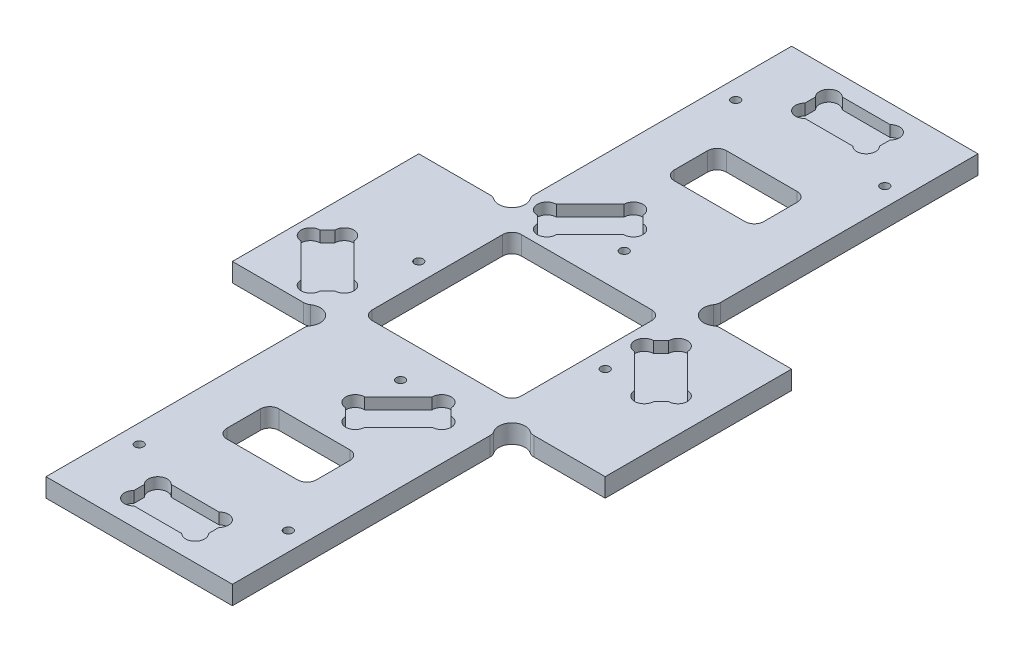
SolidWorks part; units mm, degrees
ref_plane "Front" through (0, 0, 0) normal (0, 0, 1) x (1, 0, 0)
ref_plane "Top" through (0, 0, 0) normal (0, 1, 0) x (1, 0, 0)
ref_plane "Right" through (0, 0, 0) normal (1, 0, 0) x (0, 0, -1)
sketch "Sketch1" plane through (0, 0, 0) normal (0, 1, 0) x (1, 0, 0)
  line L0 (45.4057, 247.3952) -> (45.4057, -6.6048) construction
  line L1 (13.6557, -6.6048) -> (77.1557, -6.6048)
  line L2 (13.6557, -6.6048) -> (13.6557, 247.3952)
  line L3 (13.6557, 247.3952) -> (77.1557, 247.3952)
  line L4 (77.1557, -6.6048) -> (77.1557, 247.3952)
  line L5 (13.6557, 152.1452) -> (-18.0943, 152.1452)
  line L6 (13.6557, 152.1452) -> (13.6557, 88.6452)
  line L7 (13.6557, 88.6452) -> (-18.0943, 88.6452)
  line L8 (-18.0943, 152.1452) -> (-18.0943, 88.6452)
  line L9 (77.1557, 88.6452) -> (108.9057, 88.6452)
  line L10 (108.9057, 152.1452) -> (108.9057, 88.6452)
  line L11 (77.1557, 152.1452) -> (108.9057, 152.1452)
  line L12 (77.1557, 152.1452) -> (77.1557, 88.6452)
  dimension "D1" = 63.5
  dimension "D2" = 254
  dimension "D3" = 31.75
  dimension "D4" = 63.5
  dimension "D5" = 95.25
extrude "Boss-Extrude1" add sketch "Sketch1" along normal blind 6.35 contours L5 L8 L7 L2 | L0 L3 L2 L1 | L3 L0 L1 L4 | L11 L4 L9 L10 region at (61.2807, 0, -120.3952) region at (29.5307, 0, -120.3952) region at (-2.2193, 0, -120.3952) region at (93.0307, 0, -120.3952)
sketch "Sketch2" plane through (0, 6.35, 0) normal (0, 1, 0) x (1, 0, 0)
  line L0 (13.6557, 88.6452) -> (77.1557, 152.1452) construction
  line L1 (77.1557, 152.1452) -> (77.1557, 88.6452) construction
  line L2 (77.1557, 88.6452) -> (45.4057, 120.3952) construction
  line L3 (45.4057, 120.3952) -> (45.4057, 152.1452) construction
  line L4 (45.4057, 152.1452) -> (13.6557, 152.1452) construction
  line L5 (13.6557, 152.1452) -> (45.4057, 120.3952) construction
  line L6 (2.3005, 109.6188) -> (-6.6798, 100.6386) construction
  line L7 (11.2807, 100.6386) -> (-6.6798, 118.5991)
  line L8 (-6.6798, 118.5991) -> (11.2807, 100.6386)
  line L9 (-6.6798, 118.5991) -> (-15.6601, 109.6188)
  line L10 (11.2807, 100.6386) -> (2.3005, 91.6583)
  line L11 (-15.6601, 109.6188) -> (2.3005, 91.6583)
  line L23 (11.2807, 100.6386) -> (2.3005, 91.6583)
  line L28 (43.9231, 166.4458) -> (25.9626, 148.4853)
  line L29 (43.9231, 166.4458) -> (34.9428, 175.4261)
  line L30 (34.9428, 175.4261) -> (16.9823, 157.4655)
  line L31 (25.9626, 148.4853) -> (16.9823, 157.4655)
  line L36 (43.9231, 166.4458) -> (34.9428, 175.4261)
  line L38 (6.7906, 96.1485) -> (-11.1699, 114.109) construction
  line L43 (91.7698, 115.8429) -> (73.8093, 133.8034)
  line L44 (91.7698, 115.8429) -> (100.7501, 124.8232)
  line L45 (100.7501, 124.8232) -> (82.7895, 142.7837)
  line L46 (73.8093, 133.8034) -> (82.7895, 142.7837)
  line L51 (91.7698, 115.8429) -> (100.7501, 124.8232)
  line L58 (41.1669, 67.9962) -> (59.1274, 85.9567)
  line L59 (41.1669, 67.9962) -> (50.1472, 59.0159)
  line L60 (50.1472, 59.0159) -> (68.1077, 76.9765)
  line L61 (59.1274, 85.9567) -> (68.1077, 76.9765)
  line L66 (41.1669, 67.9962) -> (50.1472, 59.0159)
  point P15 (2.3005, 109.6188)
  point P64 (42.545, 117.221)
  dimension "D1" = 22.86
  dimension "D2" = 25.4
  dimension "D3" = 12.7
  dimension "D7" = 38.1
  dimension "D6" = 4
extrude "Cut-Extrude14" cut sketch "Sketch2" against normal blind 3.81 contours L9 L11 L10 L7 | L31 L28 L29 L30 | L46 L43 L44 L45 | L61 L58 L59 L60 region at (-2.1897, 6.35, -105.1287) region at (30.4527, 6.35, -161.9557) region at (87.2797, 6.35, -129.3133) region at (54.6373, 6.35, -72.4863)
sketch "Sketch14" plane through (0, 6.35, 0) normal (0, 1, 0) x (1, 0, 0)
  line L0 (45.4057, -6.6048) -> (45.4057, 247.3952) construction
  line L1 (13.6557, -6.6048) -> (77.1557, -6.6048) construction
  line L2 (13.6557, 247.3952) -> (77.1557, 247.3952) construction
  line L3 (-18.0943, 120.3952) -> (108.9057, 120.3952) construction
  line L4 (32.7057, 241.0452) -> (58.1057, 241.0452)
  line L5 (32.7057, 241.0452) -> (32.7057, 228.3452)
  line L6 (32.7057, 228.3452) -> (58.1057, 228.3452)
  line L7 (58.1057, 241.0452) -> (58.1057, 228.3452)
  line L8 (32.7057, 241.0452) -> (58.1057, 228.3452) construction
  line L9 (32.7057, 228.3452) -> (58.1057, 241.0452) construction
  line L10 (-18.0943, 152.1452) -> (-18.0943, 88.6452) construction
  line L11 (108.9057, 152.1452) -> (108.9057, 88.6452) construction
  line L12 (32.7057, 12.4452) -> (58.1057, 12.4452)
  line L13 (58.1057, -0.2548) -> (58.1057, 12.4452)
  line L14 (32.7057, -0.2548) -> (58.1057, -0.2548)
  line L15 (32.7057, -0.2548) -> (32.7057, 12.4452)
  point P6 (45.4057, 234.6952)
  dimension "D1" = 12.7
  dimension "D2" = 25.4
  dimension "D3" = 6.35
extrude "Cut-Extrude16" cut sketch "Sketch14" against normal blind 3.81
sketch "Sketch15" plane through (0, 6.35, 0) normal (0, 1, 0) x (1, 0, 0)
  line L0 (45.4057, 247.3952) -> (45.4057, -6.6048) construction
  line L1 (13.6557, 247.3952) -> (77.1557, 247.3952) construction
  line L2 (13.6557, -6.6048) -> (77.1557, -6.6048) construction
  line L3 (45.4057, -6.6048) -> (108.9057, 120.3952) construction
  line L4 (108.9057, 152.1452) -> (108.9057, 88.6452) construction
  line L5 (108.9057, 120.3952) -> (-18.0943, 120.3952) construction
  line L6 (-18.0943, 152.1452) -> (-18.0943, 88.6452) construction
  line L7 (30.1657, 35.3052) -> (60.6457, 35.3052)
  line L8 (20.0057, 94.9952) -> (70.8057, 94.9952)
  line L9 (20.0057, 94.9952) -> (20.0057, 145.7952)
  line L10 (20.0057, 145.7952) -> (70.8057, 145.7952)
  line L11 (70.8057, 94.9952) -> (70.8057, 145.7952)
  line L12 (20.0057, 94.9952) -> (70.8057, 145.7952) construction
  line L13 (20.0057, 145.7952) -> (70.8057, 94.9952) construction
  line L14 (30.1657, 187.7052) -> (60.6457, 187.7052)
  line L15 (30.1657, 187.7052) -> (30.1657, 205.4852)
  line L16 (30.1657, 205.4852) -> (60.6457, 205.4852)
  line L17 (60.6457, 187.7052) -> (60.6457, 205.4852)
  line L18 (30.1657, 187.7052) -> (60.6457, 205.4852) construction
  line L19 (30.1657, 205.4852) -> (60.6457, 187.7052) construction
  line L20 (60.6457, 53.0852) -> (60.6457, 35.3052)
  line L21 (30.1657, 53.0852) -> (60.6457, 53.0852)
  line L22 (30.1657, 53.0852) -> (30.1657, 35.3052)
  point P6 (45.4057, 120.3952)
  point P17 (45.4057, 196.5952)
  dimension "D1" = 50.8
  dimension "D2" = 50.8
  dimension "D3" = 17.78
  dimension "D4" = 30.48
  dimension "D5" = 50.8
extrude "Cut-Extrude17" cut sketch "Sketch15" against normal through all
fillet "Fillet1" radius 3.175 12 edges at (30.1657, 3.175, -205.4852) (30.1657, 3.175, -187.7052) (60.6457, 3.175, -187.7052) (60.6457, 3.175, -205.4852) (60.6457, 3.175, -53.0852) (30.1657, 3.175, -53.0852) (30.1657, 3.175, -35.3052) (60.6457, 3.175, -35.3052) (70.8057, 3.175, -94.9952) (70.8057, 3.175, -145.7952) (20.0057, 3.175, -145.7952) (20.0057, 3.175, -94.9952)
sketch "Sketch16" plane through (0, 6.35, 0) normal (0, 1, 0) x (1, 0, 0)
  line L0 (45.4057, -6.6048) -> (45.4057, 247.3952) construction
  line L1 (13.6557, 88.6452) -> (10.4807, 88.6452)
  line L2 (13.6557, 88.6452) -> (13.6557, 85.4702)
  line L3 (13.6557, 85.4702) -> (10.4807, 85.4702)
  line L4 (10.4807, 88.6452) -> (10.4807, 85.4702)
  line L5 (13.6557, -6.6048) -> (77.1557, -6.6048) construction
  line L6 (13.6557, 247.3952) -> (77.1557, 247.3952) construction
  line L7 (45.4057, 247.3952) -> (108.9057, 120.3952) construction
  line L8 (108.9057, 152.1452) -> (108.9057, 88.6452) construction
  line L9 (108.9057, 120.3952) -> (-18.0943, 120.3952) construction
  line L10 (-18.0943, 152.1452) -> (-18.0943, 88.6452) construction
  line L11 (77.1557, 85.4702) -> (80.3307, 85.4702)
  line L12 (80.3307, 88.6452) -> (80.3307, 85.4702)
  line L13 (77.1557, 88.6452) -> (80.3307, 88.6452)
  line L14 (77.1557, 88.6452) -> (77.1557, 85.4702)
  line L16 (77.1557, 152.1452) -> (77.1557, 155.3202)
  line L17 (77.1557, 152.1452) -> (80.3307, 152.1452)
  line L18 (80.3307, 152.1452) -> (80.3307, 155.3202)
  line L19 (77.1557, 155.3202) -> (80.3307, 155.3202)
  line L20 (13.6557, 155.3202) -> (10.4807, 155.3202)
  line L21 (10.4807, 152.1452) -> (10.4807, 155.3202)
  line L22 (13.6557, 152.1452) -> (10.4807, 152.1452)
  line L23 (13.6557, 152.1452) -> (13.6557, 155.3202)
  circle A0 centre (10.4807, 85.4702) radius 4.4901
  circle A1 centre (80.3307, 85.4702) radius 4.4901
  circle A2 centre (80.3307, 155.3202) radius 4.4901
  circle A3 centre (10.4807, 155.3202) radius 4.4901
  dimension "D1" = 3.175
  dimension "D2" = 3.175
extrude "Cut-Extrude18" cut sketch "Sketch16" against normal through all contours L1 A0 L2 L3 L4 | L1 L4 L3 L2 | L13 L14 L11 L12 | L14 A1 L13 L12 L11 | L19 L16 L17 L18 | L17 A2 L16 L19 L18 | L22 L23 L20 L21 | L23 A3 L22 L21 L20 region at (12.0682, 6.35, -87.0577) region at (10.1802, 6.35, -85.1697) region at (78.7432, 6.35, -87.0577) region at (80.6312, 6.35, -85.1697) region at (78.7432, 6.35, -153.7327) region at (80.6312, 6.35, -155.6206) region at (12.0682, 6.35, -153.7327) region at (10.1802, 6.35, -155.6206)
fillet "Fillet2" radius 3.175 8 edges at (13.6557, 3.175, -158.4952) (7.3057, 3.175, -152.1452) (77.1557, 3.175, -158.4952) (83.5057, 3.175, -152.1452) (77.1557, 3.175, -82.2952) (83.5057, 3.175, -88.6452) (13.6557, 3.175, -82.2952) (7.3057, 3.175, -88.6452)
sketch "Sketch17" plane through (0, 6.35, 0) normal (0, 1, 0) x (1, 0, 0)
  line L0 (45.4057, -6.6048) -> (45.4057, 247.3952) construction
  line L1 (13.6557, -6.6048) -> (77.1557, -6.6048) construction
  line L2 (13.6557, 247.3952) -> (77.1557, 247.3952) construction
  line L3 (45.4057, 247.3952) -> (108.9057, 120.3952) construction
  line L4 (108.9057, 152.1452) -> (108.9057, 88.6452) construction
  line L5 (108.9057, 120.3952) -> (-18.0943, 120.3952) construction
  line L6 (-18.0943, 152.1452) -> (-18.0943, 88.6452) construction
  line L7 (-18.0943, 120.3952) -> (32.7057, 6.0952) construction
  line L8 (32.7057, 12.4452) -> (32.7057, -0.2548) construction
  line L9 (32.7057, 6.0952) -> (58.1057, 6.0952) construction
  line L10 (58.1057, -0.2548) -> (58.1057, 12.4452) construction
  line L11 (32.7057, 12.4452) -> (34.9917, 12.4452)
  line L12 (32.7057, 12.4452) -> (32.7057, 10.1592)
  line L13 (34.9917, 12.4452) -> (34.9917, 10.1592)
  line L14 (32.7057, 10.1592) -> (34.9917, 10.1592)
  line L15 (58.1057, 12.4452) -> (32.7057, 12.4452) construction
  line L16 (34.9917, -0.2548) -> (34.9917, 2.0312)
  line L17 (32.7057, 2.0312) -> (34.9917, 2.0312)
  line L18 (32.7057, -0.2548) -> (32.7057, 2.0312)
  line L19 (32.7057, -0.2548) -> (34.9917, -0.2548)
  line L20 (58.1057, -0.2548) -> (55.8197, -0.2548)
  line L21 (58.1057, -0.2548) -> (58.1057, 2.0312)
  line L22 (58.1057, 2.0312) -> (55.8197, 2.0312)
  line L23 (55.8197, -0.2548) -> (55.8197, 2.0312)
  line L24 (55.8197, 12.4452) -> (55.8197, 10.1592)
  line L25 (58.1057, 10.1592) -> (55.8197, 10.1592)
  line L26 (58.1057, 12.4452) -> (58.1057, 10.1592)
  line L27 (58.1057, 12.4452) -> (55.8197, 12.4452)
  line L28 (58.1057, 241.0452) -> (58.1057, 238.7592)
  line L29 (58.1057, 238.7592) -> (55.8197, 238.7592)
  line L30 (55.8197, 241.0452) -> (55.8197, 238.7592)
  line L31 (58.1057, 241.0452) -> (55.8197, 241.0452)
  line L32 (58.1057, 228.3452) -> (55.8197, 228.3452)
  line L33 (58.1057, 228.3452) -> (58.1057, 230.6312)
  line L34 (58.1057, 230.6312) -> (55.8197, 230.6312)
  line L35 (55.8197, 228.3452) -> (55.8197, 230.6312)
  line L36 (34.9917, 228.3452) -> (34.9917, 230.6312)
  line L37 (32.7057, 230.6312) -> (34.9917, 230.6312)
  line L38 (32.7057, 228.3452) -> (32.7057, 230.6312)
  line L39 (32.7057, 228.3452) -> (34.9917, 228.3452)
  line L40 (32.7057, 241.0452) -> (34.9917, 241.0452)
  line L41 (32.7057, 241.0452) -> (32.7057, 238.7592)
  line L42 (32.7057, 238.7592) -> (34.9917, 238.7592)
  line L43 (34.9917, 241.0452) -> (34.9917, 238.7592)
  circle A0 centre (34.9917, 10.1592) radius 3.2329
  circle A1 centre (34.9917, 2.0312) radius 3.2329
  circle A2 centre (55.8197, 2.0312) radius 3.2329
  circle A3 centre (55.8197, 10.1592) radius 3.2329
  circle A4 centre (55.8197, 238.7592) radius 3.2329
  circle A5 centre (55.8197, 230.6312) radius 3.2329
  circle A6 centre (34.9917, 230.6312) radius 3.2329
  circle A7 centre (34.9917, 238.7592) radius 3.2329
  dimension "D1" = 2.286
  dimension "D2" = 2.286
extrude "Cut-Extrude19" cut sketch "Sketch17" against normal blind 3.81 contours L43 L40 L41 L42 | L41 A7 L40 L43 L42 | L31 A4 L28 L29 L30 | L28 L31 L30 L29 | L33 A5 L32 L35 L34 | L35 L32 L33 L34 | L39 A6 L38 L37 L36 | L38 L39 L36 L37 | L19 A1 L18 L17 L16 | L18 L19 L16 L17 | L12 A0 L11 L13 L14 | L12 L14 L13 L11 | L27 A3 L26 L25 L24 | L26 L27 L24 L25 | L21 A2 L20 L23 L22 | L23 L20 L21 L22 region at (33.8487, 6.35, -11.3022) region at (35.208, 6.35, -9.9428) region at (33.8487, 6.35, -0.8882) region at (35.208, 6.35, -2.2475) region at (56.9627, 6.35, -0.8882) region at (55.6033, 6.35, -2.2475) region at (56.9627, 6.35, -11.3022) region at (55.6033, 6.35, -9.9428) region at (56.9627, 6.35, -239.9022) region at (55.6033, 6.35, -238.5428) region at (56.9627, 6.35, -229.4882) region at (55.6033, 6.35, -230.8475) region at (33.8487, 6.35, -229.4882) region at (35.208, 6.35, -230.8475) region at (33.8487, 6.35, -239.9022) region at (35.208, 6.35, -238.5428)
sketch "Sketch18" plane through (0, 6.35, 0) normal (0, 1, 0) x (1, 0, 0)
  line L0 (-15.6601, 109.6188) -> (-14.0436, 111.2353)
  line L1 (-15.6601, 109.6188) -> (-14.0436, 108.0024)
  line L2 (-14.0436, 111.2353) -> (-12.4272, 109.6188)
  line L3 (-14.0436, 108.0024) -> (-12.4272, 109.6188)
  line L4 (-6.6798, 118.5991) -> (-15.6601, 109.6188) construction
  line L5 (-11.1699, 114.109) -> (6.7906, 96.1485) construction
  line L6 (11.2807, 100.6386) -> (2.3005, 91.6583) construction
  line L7 (6.7906, 96.1485) -> (2.3005, 109.6188) construction
  line L8 (11.2807, 100.6386) -> (-6.6798, 118.5991) construction
  line L9 (2.3005, 109.6188) -> (-6.6798, 100.6386) construction
  line L10 (-15.6601, 109.6188) -> (2.3005, 91.6583) construction
  line L11 (-8.2962, 116.9827) -> (-6.6798, 115.3662)
  line L12 (-5.0634, 116.9827) -> (-6.6798, 115.3662)
  line L13 (-6.6798, 118.5991) -> (-5.0634, 116.9827)
  line L14 (-6.6798, 118.5991) -> (-8.2962, 116.9827)
  line L15 (11.2807, 100.6386) -> (9.6643, 99.0221)
  line L16 (11.2807, 100.6386) -> (9.6643, 102.255)
  line L17 (9.6643, 102.255) -> (8.0478, 100.6386)
  line L18 (9.6643, 99.0221) -> (8.0478, 100.6386)
  line L19 (3.9169, 93.2748) -> (2.3005, 94.8912)
  line L20 (0.684, 93.2748) -> (2.3005, 94.8912)
  line L21 (2.3005, 91.6583) -> (0.684, 93.2748)
  line L22 (2.3005, 91.6583) -> (3.9169, 93.2748)
  line L23 (45.4057, 145.7952) -> (45.4057, 94.9952) construction
  line L24 (67.6307, 145.7952) -> (23.1807, 145.7952) construction
  line L25 (23.1807, 94.9952) -> (67.6307, 94.9952) construction
  line L26 (45.4057, 94.9952) -> (70.8057, 120.3952) construction
  line L27 (70.8057, 98.1702) -> (70.8057, 142.6202) construction
  line L28 (70.8057, 120.3952) -> (20.0057, 120.3952) construction
  line L29 (20.0057, 142.6202) -> (20.0057, 98.1702) construction
  circle A0 centre (-12.4272, 109.6188) radius 3.2329
  circle A1 centre (-6.6798, 115.3662) radius 3.2329
  circle A2 centre (8.0478, 100.6386) radius 3.2329
  circle A3 centre (2.3005, 94.8912) radius 3.2329
  dimension "D1" = 2.286
  dimension "D2" = 2.286
extrude "Cut-Extrude20" cut sketch "Sketch18" against normal blind 3.81 contours L1 L3 L2 L0 | L1 A0 L0 L2 L3 | L13 L14 L11 L12 | L14 A1 L13 L12 L11 | L18 L15 L16 L17 | L16 A2 L15 L18 L17 | L21 L22 L19 L20 | L22 A3 L21 L20 L19 region at (-14.0436, 6.35, -109.6188) region at (-12.1212, 6.35, -109.6188) region at (-6.6798, 6.35, -116.9827) region at (-6.6798, 6.35, -115.0602) region at (9.6643, 6.35, -100.6386) region at (7.7419, 6.35, -100.6386) region at (2.3005, 6.35, -93.2748) region at (2.3005, 6.35, -95.1972)
sketch "Sketch19" plane through (0, 6.35, 0) normal (0, 1, 0) x (1, 0, 0)
  line L0 (34.9428, 175.4261) -> (33.3264, 173.8096)
  line L1 (34.9428, 175.4261) -> (36.5593, 173.8096)
  line L2 (33.3264, 173.8096) -> (34.9428, 172.1932)
  line L3 (36.5593, 173.8096) -> (34.9428, 172.1932)
  line L4 (43.9231, 166.4458) -> (34.9428, 175.4261) construction
  line L5 (34.9428, 175.4261) -> (16.9823, 157.4655) construction
  line L6 (39.433, 170.9359) -> (21.4725, 152.9754) construction
  line L7 (25.9626, 148.4853) -> (16.9823, 157.4655) construction
  line L8 (25.9626, 166.4458) -> (34.9428, 157.4655) construction
  line L9 (43.9231, 166.4458) -> (25.9626, 148.4853) construction
  line L11 (42.3067, 164.8294) -> (40.6902, 166.4458)
  line L12 (42.3067, 168.0622) -> (40.6902, 166.4458)
  line L13 (43.9231, 166.4458) -> (42.3067, 168.0622)
  line L14 (43.9231, 166.4458) -> (42.3067, 164.8294)
  line L15 (25.9626, 148.4853) -> (27.579, 150.1017)
  line L16 (25.9626, 148.4853) -> (24.3461, 150.1017)
  line L17 (24.3461, 150.1017) -> (25.9626, 151.7182)
  line L18 (27.579, 150.1017) -> (25.9626, 151.7182)
  line L19 (18.5988, 159.082) -> (20.2152, 157.4655)
  line L20 (18.5988, 155.8491) -> (20.2152, 157.4655)
  line L21 (16.9823, 157.4655) -> (18.5988, 155.8491)
  line L22 (16.9823, 157.4655) -> (18.5988, 159.082)
  line L23 (82.7895, 142.7837) -> (81.1731, 141.1672)
  line L24 (82.7895, 142.7837) -> (84.406, 141.1672)
  line L25 (81.1731, 141.1672) -> (82.7895, 139.5508)
  line L26 (84.406, 141.1672) -> (82.7895, 139.5508)
  line L27 (73.8093, 133.8034) -> (82.7895, 142.7837) construction
  line L28 (78.2994, 138.2935) -> (96.2599, 120.333) construction
  line L29 (91.7698, 115.8429) -> (100.7501, 124.8232) construction
  line L30 (91.7698, 133.8034) -> (82.7895, 124.8232) construction
  line L34 (75.4257, 135.4199) -> (77.0422, 133.8034)
  line L35 (75.4257, 132.187) -> (77.0422, 133.8034)
  line L36 (73.8093, 133.8034) -> (75.4257, 132.187)
  line L37 (73.8093, 133.8034) -> (75.4257, 135.4199)
  line L38 (100.7501, 124.8232) -> (82.7895, 142.7837) construction
  line L39 (91.7698, 115.8429) -> (73.8093, 133.8034) construction
  line L40 (99.1336, 123.2067) -> (97.5172, 124.8232)
  line L41 (99.1336, 126.4396) -> (97.5172, 124.8232)
  line L42 (100.7501, 124.8232) -> (99.1336, 126.4396)
  line L43 (100.7501, 124.8232) -> (99.1336, 123.2067)
  line L44 (91.7698, 115.8429) -> (93.3862, 117.4593)
  line L45 (91.7698, 115.8429) -> (90.1534, 117.4593)
  line L46 (90.1534, 117.4593) -> (91.7698, 119.0758)
  line L47 (93.3862, 117.4593) -> (91.7698, 119.0758)
  line L48 (45.657, 63.5061) -> (63.6175, 81.4666) construction
  line L49 (41.1669, 67.9962) -> (50.1472, 59.0159) construction
  line L50 (59.1274, 85.9567) -> (68.1077, 76.9765) construction
  line L51 (50.1472, 76.9765) -> (59.1274, 67.9962) construction
  line L52 (41.1669, 67.9962) -> (59.1274, 85.9567) construction
  line L53 (50.1472, 59.0159) -> (68.1077, 76.9765) construction
  line L54 (41.1669, 67.9962) -> (42.7833, 69.6126)
  line L55 (41.1669, 67.9962) -> (42.7833, 66.3798)
  line L56 (42.7833, 69.6126) -> (44.3998, 67.9962)
  line L57 (42.7833, 66.3798) -> (44.3998, 67.9962)
  line L59 (51.7636, 60.6324) -> (50.1472, 62.2488)
  line L60 (48.5307, 60.6324) -> (50.1472, 62.2488)
  line L61 (50.1472, 59.0159) -> (48.5307, 60.6324)
  line L62 (50.1472, 59.0159) -> (51.7636, 60.6324)
  line L63 (68.1077, 76.9765) -> (66.4912, 75.36)
  line L64 (68.1077, 76.9765) -> (66.4912, 78.5929)
  line L65 (66.4912, 78.5929) -> (64.8748, 76.9765)
  line L66 (66.4912, 75.36) -> (64.8748, 76.9765)
  line L67 (57.511, 84.3403) -> (59.1274, 82.7238)
  line L68 (60.7439, 84.3403) -> (59.1274, 82.7238)
  line L69 (59.1274, 85.9567) -> (60.7439, 84.3403)
  line L70 (59.1274, 85.9567) -> (57.511, 84.3403)
  circle A0 centre (34.9428, 172.1932) radius 3.2329
  circle A1 centre (40.6902, 166.4458) radius 3.2329
  circle A2 centre (25.9626, 151.7182) radius 3.2329
  circle A3 centre (20.2152, 157.4655) radius 3.2329
  circle A4 centre (82.7895, 139.5508) radius 3.2329
  circle A5 centre (77.0422, 133.8034) radius 3.2329
  circle A6 centre (97.5172, 124.8232) radius 3.2329
  circle A7 centre (91.7698, 119.0758) radius 3.2329
  circle A8 centre (44.3998, 67.9962) radius 3.2329
  circle A9 centre (50.1472, 62.2488) radius 3.2329
  circle A10 centre (64.8748, 76.9765) radius 3.2329
  circle A11 centre (59.1274, 82.7238) radius 3.2329
  dimension "D1" = 2.286
  dimension "D2" = 2.286
  dimension "D3" = 2.286
  dimension "D4" = 2.286
  dimension "D5" = 2.286
  dimension "D6" = 2.286
extrude "Cut-Extrude22" cut sketch "Sketch19" against normal blind 3.81 contours L55 A8 L54 L56 L57 | L61 L62 L59 L60 | L62 A9 L61 L60 L59 | L69 L70 L67 L68 | L70 A11 L69 L68 L67 | L66 L63 L64 L65 | L64 A10 L63 L66 L65 | L44 L47 L46 L45 | L44 A7 L45 L46 L47 | L43 L42 L41 L40 | L42 A6 L43 L40 L41 | L26 L24 L23 L25 | L23 A4 L24 L26 L25 | L37 L36 L35 L34 | L36 A5 L37 L34 L35 | L15 A2 L16 L17 L18 | L15 L18 L17 L16 | L22 L21 L20 L19 | L21 A3 L22 L19 L20 | L3 L1 L0 L2 | L0 A0 L1 L3 L2 | L14 L13 L12 L11 | L13 A1 L14 L11 L12 | L55 L57 L56 L54 | L56 L57 L55 L54 | L18 L17 L16 L15 region at (34.9428, 6.35, -173.8096) region at (34.9428, 6.35, -171.8872) region at (40.3842, 6.35, -166.4458) region at (42.3067, 6.35, -166.4458) region at (25.9626, 6.35, -150.1017) region at (25.9626, 6.35, -152.0241) region at (20.5212, 6.35, -157.4655) region at (18.5988, 6.35, -157.4655) region at (82.7895, 6.35, -141.1672) region at (82.7895, 6.35, -139.2448) region at (77.3481, 6.35, -133.8034) region at (75.4257, 6.35, -133.8034) region at (97.2112, 6.35, -124.8232) region at (99.1336, 6.35, -124.8232) region at (91.7698, 6.35, -117.4593) region at (91.7698, 6.35, -119.3818) region at (42.7833, 6.35, -67.9962) region at (44.7058, 6.35, -67.9962) region at (50.1472, 6.35, -60.6324) region at (50.1472, 6.35, -62.5548) region at (66.4912, 6.35, -76.9765) region at (64.5688, 6.35, -76.9765) region at (59.1274, 6.35, -84.3403) region at (59.1274, 6.35, -82.4179)
sketch "Sketch20" plane through (0, 6.35, 0) normal (0, 1, 0) x (1, 0, 0)
  line L0 (45.4057, 247.3952) -> (45.4057, -6.6048) construction
  line L1 (13.6557, 247.3952) -> (77.1557, 247.3952) construction
  line L2 (13.6557, -6.6048) -> (77.1557, -6.6048) construction
  line L3 (45.4057, -6.6048) -> (108.9057, 120.3952) construction
  line L4 (108.9057, 152.1452) -> (108.9057, 88.6452) construction
  line L5 (108.9057, 120.3952) -> (-18.0943, 120.3952) construction
  line L6 (-18.0943, 152.1452) -> (-18.0943, 88.6452) construction
  circle A0 centre (20.0057, 221.9952) radius 1.4732
  circle A1 centre (70.8057, 221.9952) radius 1.4732
  circle A2 centre (70.8057, 18.7952) radius 1.4732
  circle A3 centre (20.0057, 18.7952) radius 1.4732
  circle A4 centre (13.6557, 120.3952) radius 1.4732
  circle A5 centre (77.1557, 120.3952) radius 1.4732
  dimension "D1" = 2.9464
  dimension "D2" = 25.4
  dimension "D3" = 25.4
  dimension "D4" = 2.9464
  dimension "D5" = 31.75
extrude "Cut-Extrude23" cut sketch "Sketch20" against normal through all and the other way through all
sketch "Sketch21" plane through (0, 6.35, 0) normal (0, 1, 0) x (1, 0, 0)
  line L0 (13.6557, 247.3952) -> (77.1557, 247.3952) construction
  line L1 (-18.0943, 120.3952) -> (108.9057, 120.3952) construction
  line L2 (-18.0943, 152.1452) -> (-18.0943, 88.6452) construction
  line L3 (108.9057, 152.1452) -> (108.9057, 88.6452) construction
  circle A0 centre (45.5421, 158.4952) radius 1.4732
  circle A1 centre (45.5421, 82.2952) radius 1.4732
  point P0 (45.5421, 158.4952)
  dimension "D2" = 2.9464
  dimension "D1" = 88.9
extrude "Cut-Extrude24" cut sketch "Sketch21" against normal through all
